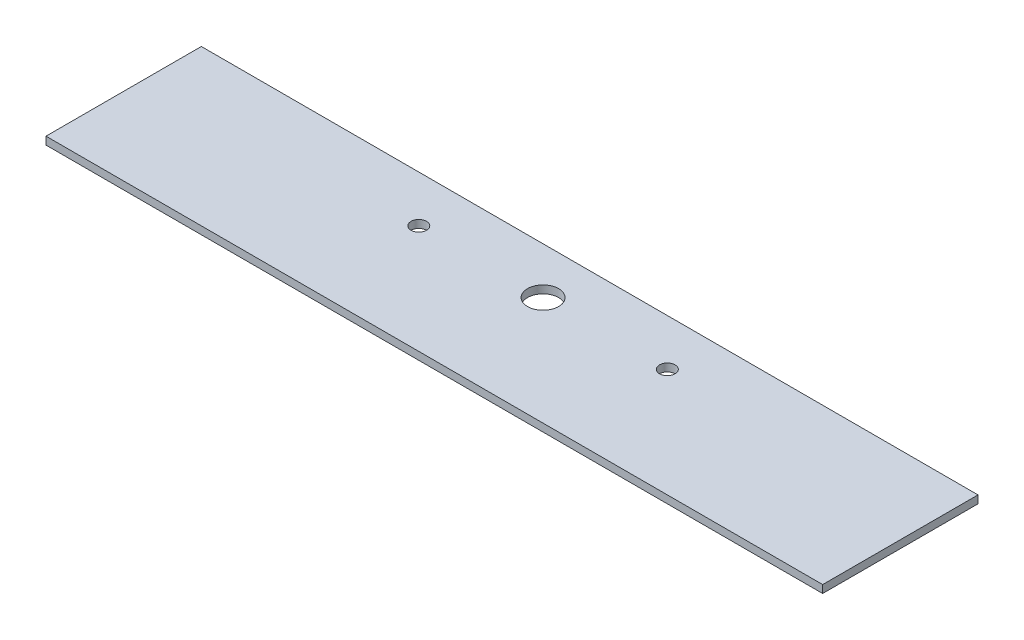
SolidWorks part; units mm, degrees
ref_plane "Front Plane" through (0, 0, 0) normal (0, 0, 1) x (1, 0, 0)
ref_plane "Top Plane" through (0, 0, 0) normal (0, 1, 0) x (1, 0, 0)
ref_plane "Right Plane" through (0, 0, 0) normal (1, 0, 0) x (0, 0, -1)
sketch "Sketch1" plane through (0, 0, 0) normal (0, 1, 0) x (1, 0, 0)
  line L1 (0, 0) -> (500, 0)
  line L2 (0, 0) -> (0, 100)
  line L3 (0, 100) -> (500, 100)
  line L4 (500, 0) -> (500, 100)
  dimension "D1" = 500
  dimension "D2" = 100
extrude "Boss-Extrude1" add sketch "Sketch1" along normal blind 5 contours L3 L4 L1 L2
sketch "Sketch3" plane through (0, 5, 0) normal (0, 1, 0) x (1, 0, 0)
  circle A0 centre (250, 70) radius 10
extrude "Cut-Extrude1" cut sketch "Sketch3" against normal through all
sketch "Sketch4" plane through (0, 5, 0) normal (0, 1, 0) x (1, 0, 0)
  circle A0 centre (170, 70) radius 5
extrude "Cut-Extrude2" cut sketch "Sketch4" against normal through all
sketch "Sketch5" plane through (0, 5, 0) normal (0, 1, 0) x (1, 0, 0)
  circle A0 centre (330, 70) radius 5
extrude "Cut-Extrude3" cut sketch "Sketch5" against normal through all
